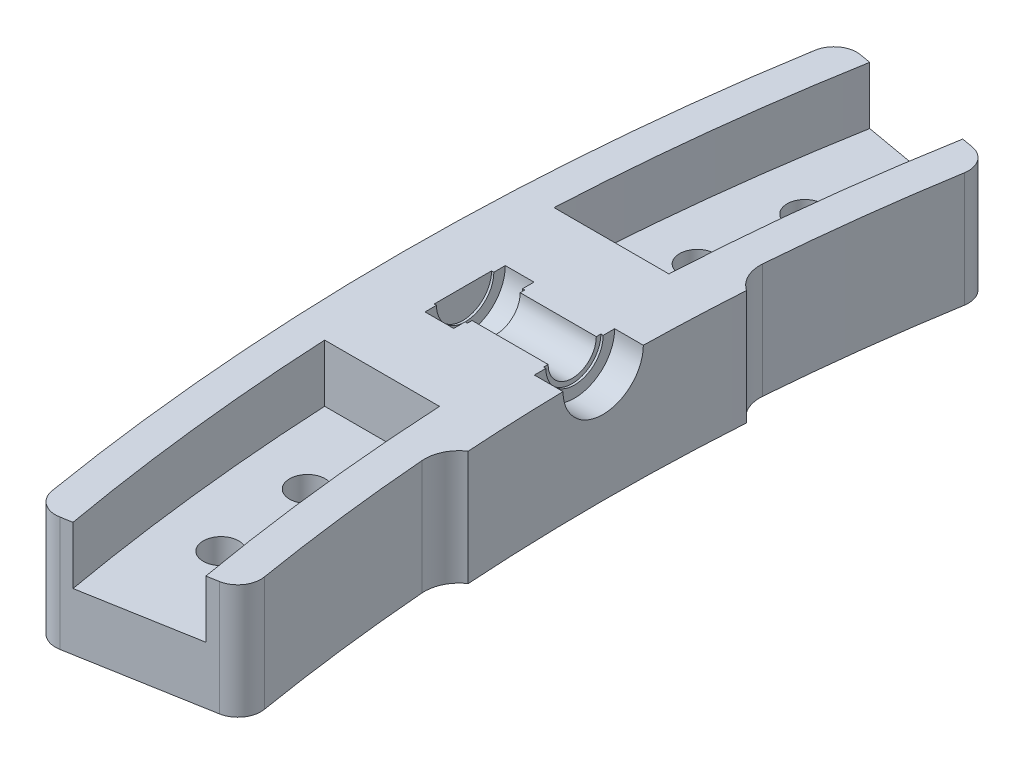
SolidWorks part; units mm, degrees
ref_plane "Front Plane" through (0, 0, 0) normal (0, 0, 1) x (1, 0, 0)
ref_plane "Top Plane" through (0, 0, 0) normal (0, 1, 0) x (1, 0, 0)
ref_plane "Right Plane" through (0, 0, 0) normal (1, 0, 0) x (0, 0, -1)
sketch "Sketch1" plane through (0, 0, 0) normal (0, 1, 0) x (1, 0, 0)
  line L0 (0, 0) -> (-196.9616, -34.7296) construction
  line L1 (0, 0) -> (-196.9616, 34.7296) construction
  line L2 (0, 0) -> (-195, 0) construction
  line L3 (-196.9616, 34.7296) -> (-187.1135, 32.9932)
  line L4 (-187.1135, -32.9932) -> (-196.9616, -34.7296)
  line L5 (0, 0) -> (-199.916, -35.2506) construction
  line L6 (0, 0) -> (-199.916, 35.2506) construction
  line L7 (-199.916, 35.2506) -> (-184.159, 32.4722)
  line L8 (-199.916, -35.2506) -> (-184.159, -32.4722)
  arc A0 (-196.9616, 34.7296) -> (-196.9616, -34.7296) centre (0, 0) ccw
  arc A1 (-187.1135, 32.9932) -> (-187.1135, -32.9932) centre (0, 0) ccw
  arc A2 (-192.0375, -33.8614) -> (-192.0375, 33.8614) centre (0, 0) cw construction
  arc A4 (-184.159, 32.4722) -> (-184.159, -32.4722) centre (0, 0) ccw
  arc A5 (-199.916, 35.2506) -> (-199.916, -35.2506) centre (0, 0) ccw
  dimension "D1" = 200
  dimension "D2" = 190
  dimension "D3" = 5
  dimension "D5" = 187
  dimension "D6" = 203
  dimension "D4" = 20
extrude "Boss-Extrude1" add sketch "Sketch1" along normal blind 10 contours A1 L3 A0 L4 | L7 A5 L8 A0 | A4 L7 A1 L8 region at (-200.4823, 0, 0) region at (-194.054, 0, 0) region at (-187.5484, 0, 0)
ref_plane "Plane1" through (-195, 0, 0) normal (1, 0, 0) x (0, 0, -1)
sketch "Sketch15" plane through (0, 10, 0) normal (0, 1, 0) x (1, 0, 0)
  line L0 (-187.1135, -32.9932) -> (-196.9616, -34.7296) construction
  line L1 (-185, 10) -> (-205, 10)
  line L2 (-185, 10) -> (-185, -10)
  line L3 (-185, -10) -> (-205, -10)
  line L4 (-205, 10) -> (-205, -10)
  line L5 (-185, 10) -> (-205, -10) construction
  line L6 (-185, -10) -> (-205, 10) construction
  line L7 (-196.9616, 34.7296) -> (-187.1135, 32.9932) construction
  line L8 (-187.1135, -32.9932) -> (-196.9616, -34.7296)
  line L9 (-196.9616, 34.7296) -> (-187.1135, 32.9932)
  arc A2 (-187.1135, 32.9932) -> (-187.1135, -32.9932) centre (0, 0) ccw construction
  arc A3 (-196.9616, 34.7296) -> (-196.9616, -34.7296) centre (0, 0) ccw construction
  arc A4 (-187.1135, 32.9932) -> (-187.1135, -32.9932) centre (0, 0) ccw
  arc A5 (-196.9616, 34.7296) -> (-196.9616, -34.7296) centre (0, 0) ccw
  point P0 (-195, 0)
  line M5 (-199.916, -35.2506) -> (-184.159, -32.4722)
  line M7 (-184.159, 32.4722) -> (-199.916, 35.2506)
  dimension "D1" = 20
  dimension "D2" = 20
extrude "Cut-Extrude1" cut sketch "Sketch15" against normal blind 5 contours A5 L1 A4 M7 | L3 A5 A4 M5 region at (-193.6958, 10, -21.9638) region at (-193.6958, 10, 21.9638)
ref_plane "Plane2" through (-195, 0, 0) normal (-1, 0, 0) x (0, 0, 1)
sketch "Sketch12" plane through (0, 0, 0) normal (0, 1, 0) x (1, 0, 0)
  line L0 (0, 0) -> (-194.258, -16.9954) construction
  line L1 (0, 0) -> (-193.3317, -25.4526) construction
  line L2 (0, 0) -> (-195, 0) construction
  line L3 (0, 0) -> (-195, 0) construction
  line L4 (0, 0) -> (-194.258, 16.9954) construction
  line L5 (0, 0) -> (-193.3317, 25.4526) construction
  arc A0 (-192.0375, 33.8614) -> (-192.0375, -33.8614) centre (0, 0) ccw construction
  dimension "D1" = 10
  dimension "D2" = 15
hole_wizard "Ø3.1 (3.1) Diameter Hole2" positions "Sketch18" profile "Sketch17" hole size "Ø3.1" standard "ISO" end condition through all
sketch "Sketch18" plane through (0, 0, 0) normal (0, -1, 0) x (-1, 0, 0)
  point P0 (193.3317, -25.4526)
  point P3 (194.258, -16.9954)
  point P6 (194.258, 16.9954)
  point P9 (193.3317, 25.4526)
sketch "Sketch17" plane through (-193.3317, 0, 25.4526) normal (1, 0, 0) x (0, 0, -1)
  line L0 (0, 0) -> (0, 10)
  line L1 (0, 10) -> (1.55, 10)
  line L2 (1.55, 10) -> (1.55, 0)
  line L5 (1.55, 0) -> (0, 0)
  line L11 (0, -6.35) -> (0, 107.95) construction
  dimension "Thru Hole Dia." = 3.1
  dimension "Thru Hole Depth" = 10
sketch "Sketch19" plane through (0, 0, 0) normal (0, 1, 0) x (1, 0, 0)
  line L0 (0, 0) -> (-185.1028, -12.1323) construction
  line L1 (0, 0) -> (-185.5, 0) construction
  line L2 (-185.1028, -12.1323) -> (-186.5996, -12.2304)
  line L3 (-185.1028, 12.1323) -> (-186.5996, 12.2304)
  arc A0 (-185.1028, 12.1323) -> (-185.1028, -12.1323) centre (0, 0) ccw
  arc A1 (-184.159, 32.4722) -> (-184.159, -32.4722) centre (0, 0) ccw construction
  arc A2 (-186.5996, 12.2304) -> (-186.5996, -12.2304) centre (0, 0) ccw
  dimension "D1" = 185.5
  dimension "D2" = 3.75
extrude "Boss-Extrude2" add sketch "Sketch19" along normal blind 10
fillet "Fillet1" radius 3 2 edges at (-186.5996, 5, -12.2304) (-186.5996, 5, 12.2304)
fillet "Fillet2" radius 2 4 edges at (-199.916, 5, -35.2506) (-199.916, 5, 35.2506) (-184.159, 5, 32.4722) (-184.159, 5, -32.4722)
sketch "Sketch20" plane through (0, 10, 0) normal (0, 1, 0) x (1, 0, 0)
  line L0 (0, 0) -> (-185, 0) construction
  line L1 (-185, 0) -> (-197.5, 0) construction
  dimension "D1" = 185
  dimension "D2" = 12.5
ref_plane "Plane3" through (-197.5, 0, 0) normal (1, 0, 0) x (0, 0, -1)
sketch "Sketch21" plane through (-197.5, 0, 0) normal (1, 0, 0) x (0, 0, -1)
  line L0 (12.1323, 10) -> (-12.1323, 10) construction
  circle A0 centre (0, 10) radius 2.1
  dimension "D1" = 4.2
extrude "Cut-Extrude2" cut sketch "Sketch21" along normal through all
sketch "Sketch22" plane through (-197.5, 0, 0) normal (1, 0, 0) x (0, 0, -1)
  line L0 (-2.1, 10) -> (2.1, 10) construction
  circle A0 centre (0, 10) radius 3.5
  dimension "D1" = 7
extrude "Cut-Extrude3" cut sketch "Sketch22" along normal blind 2.5
sketch "Sketch23" plane through (-197.5, 0, 0) normal (1, 0, 0) x (0, 0, -1)
  line L0 (-3.5, 10) -> (3.5, 10) construction
  circle A0 centre (0, 10) radius 2.5
  dimension "D1" = 5
extrude "Cut-Extrude4" cut sketch "Sketch23" against normal blind 0.2 and the other way blind 2.7
sketch "Sketch24" plane through (0, 10, 0) normal (0, 1, 0) x (1, 0, 0)
  line L0 (-185.5, 0) -> (-197.7, 0) construction
  line L1 (-197.7, -2.5) -> (-197.7, 2.5) construction
  line L3 (-187.967, 0) -> (-185.467, 0)
  line L4 (-187.967, 0) -> (-187.967, 3.5)
  line L5 (-187.967, 3.5) -> (-185.467, 3.5)
  line L6 (-185.467, 0) -> (-185.467, 3.5)
  arc A0 (-185.4881, 2.1) -> (-185.4881, -2.1) centre (0, 0) ccw construction
  arc A1 (-185.1028, 12.1323) -> (-185.4881, 2.1) centre (0, 0) ccw construction
  dimension "D1" = 2.5
  dimension "D2" = 7
revolve "Cut-Revolve1" cut sketch "Sketch24" angle 360 about L0
sketch "Sketch25" plane through (-187.967, 0, 0) normal (1, 0, 0) x (0, 0, -1)
  line L0 (-2.5, 10) -> (2.5, 10) construction
  circle A0 centre (0, 10) radius 2.5
  dimension "D1" = 5
extrude "Cut-Extrude5" cut sketch "Sketch25" against normal blind 0.2
